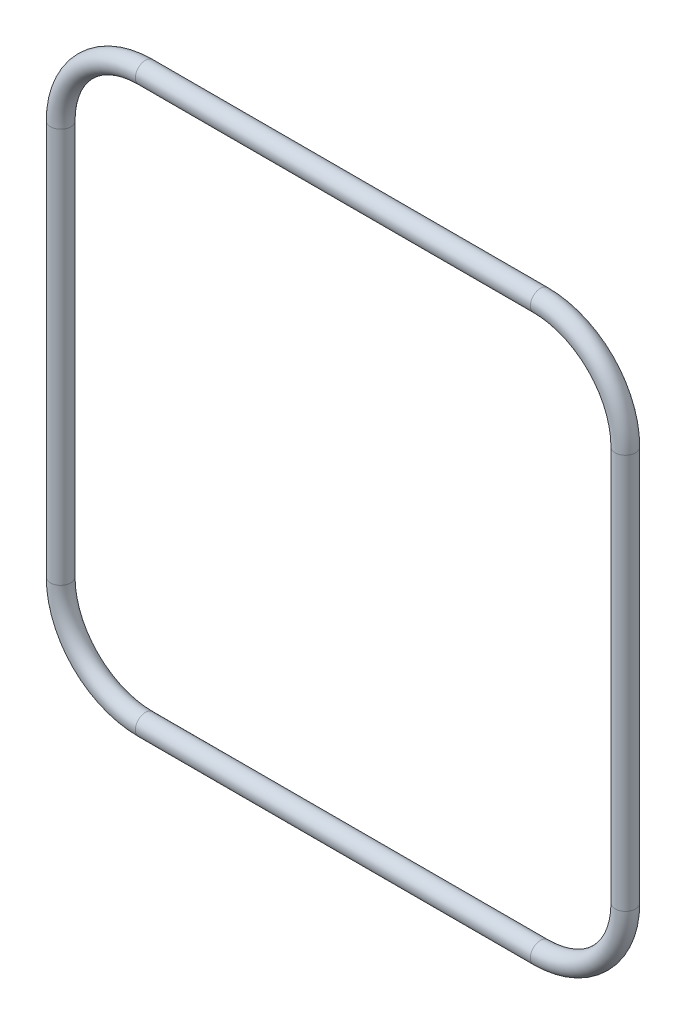
SolidWorks part; units mm, degrees
ref_plane "Front Plane" through (0, 0, 0) normal (0, 0, 1) x (1, 0, 0)
ref_plane "Top Plane" through (0, 0, 0) normal (0, 1, 0) x (1, 0, 0)
ref_plane "Right Plane" through (0, 0, 0) normal (1, 0, 0) x (0, 0, -1)
sketch "Sketch1" plane through (0, 0, 0) normal (0, 0, 1) x (1, 0, 0)
  line L0 (18, 82) -> (82, 18)
  line L1 (82, 82) -> (18, 18)
  line L4 (2.5, 82) -> (2.5, 18)
  line L5 (18, 2.5) -> (82, 2.5)
  line L6 (97.5, 18) -> (97.5, 82)
  line L7 (82, 97.5) -> (18, 97.5)
  line L8 (4.25, 82) -> (4.25, 18)
  line L9 (18, 4.25) -> (82, 4.25)
  line L10 (95.75, 18) -> (95.75, 82)
  line L11 (82, 95.75) -> (18, 95.75)
  line L12 (6, 82) -> (6, 18)
  line L13 (18, 6) -> (82, 6)
  line L14 (94, 18) -> (94, 82)
  line L15 (82, 94) -> (18, 94)
  circle A0 centre (50, 50) radius 6.1545
  arc A4 (18, 97.5) -> (2.5, 82) centre (18, 82) ccw
  arc A5 (2.5, 18) -> (18, 2.5) centre (18, 18) ccw
  arc A6 (82, 2.5) -> (97.5, 18) centre (82, 18) ccw
  arc A7 (97.5, 82) -> (82, 97.5) centre (82, 82) ccw
  arc A8 (18, 95.75) -> (4.25, 82) centre (18, 82) ccw
  arc A9 (4.25, 18) -> (18, 4.25) centre (18, 18) ccw
  arc A10 (82, 4.25) -> (95.75, 18) centre (82, 18) ccw
  arc A11 (95.75, 82) -> (82, 95.75) centre (82, 82) ccw
  arc A12 (18, 94) -> (6, 82) centre (18, 82) ccw
  arc A13 (6, 18) -> (18, 6) centre (18, 18) ccw
  arc A14 (82, 6) -> (94, 18) centre (82, 18) ccw
  arc A15 (94, 82) -> (82, 94) centre (82, 82) ccw
  dimension "D1" = 1.75
  dimension "D2" = 1.75
sweep "Sweep1" add path "Sketch1" circular profile diameter 3.3 parameters "D3"=3.3
sketch "Sketch5" plane through (0, 0, 0) normal (0, 0, 1) x (1, 0, 0)
  line L0 (5.9, 50) -> (94.1, 50)
  line L1 (5.9, 18) -> (5.9, 82) construction
  line L2 (94.1, 82) -> (94.1, 18) construction
  line L3 (50, 94.1) -> (50, 5.9)
  line L4 (18, 94.1) -> (82, 94.1) construction
  line L5 (82, 5.9) -> (18, 5.9) construction
ref_point "Point1"
ref_axis "Axis1" through (50, 50, 0) along (0, 0, 1)
ref_plane "Plane3" through (0, 0, 1.65) normal (0, 0, 1) x (1, 0, 0)
